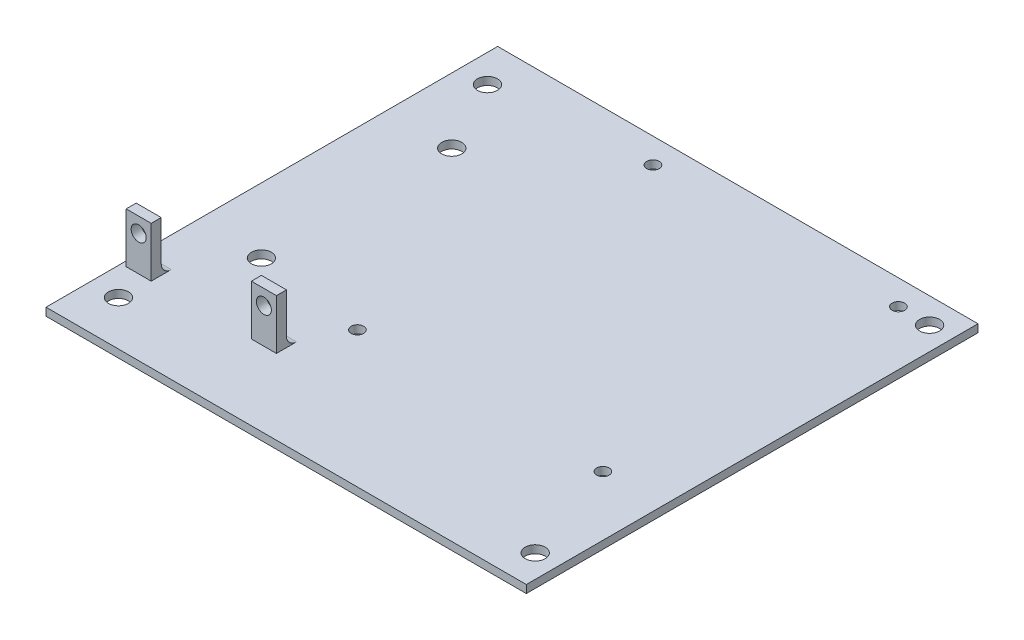
SolidWorks part; units mm, degrees
other "DetailItem3"
material "ABS"
ref_plane "Front Plane" through (0, 0, 0) normal (0, 0, 1) x (1, 0, 0)
ref_plane "Top Plane" through (0, 0, 0) normal (0, 1, 0) x (1, 0, 0)
ref_plane "Right Plane" through (0, 0, 0) normal (1, 0, 0) x (0, 0, -1)
sketch "Sketch1" plane through (0, 0, 0) normal (0, 1, 0) x (1, 0, 0)
  line L1 (-32.2441, 108.719) -> (64.6459, 108.719)
  line L2 (-32.2441, 108.719) -> (-32.2441, 18.549)
  line L3 (-32.2441, 18.549) -> (64.6459, 18.549)
  line L4 (64.6459, 108.719) -> (64.6459, 18.549)
  dimension "D1" = 96.89
  dimension "D2" = 90.17
extrude "PCB" add sketch "Sketch1" along normal blind 1.57
sketch "Sketch2" plane through (0, 1.57, 0) normal (0, 1, 0) x (1, 0, 0)
  line L0 (64.6459, 18.549) -> (64.6459, 108.719) construction
  line L1 (-32.2441, 18.549) -> (64.6459, 18.549) construction
  circle A0 centre (59.5659, 24.899) radius 2
  circle A1 centre (-26.1641, 27.439) radius 2
  circle A2 centre (-26.1641, 101.099) radius 2
  circle A3 centre (59.5659, 103.639) radius 2
  dimension "D3" = 4
  dimension "D6" = 4
  dimension "D11" = 4
  dimension "D12" = 4
  dimension "D1" = 5.08
  dimension "D2" = 6.35
  dimension "D4" = 90.81
  dimension "D5" = 8.89
  dimension "D7" = 90.81
  dimension "D8" = 5.08
  dimension "D9" = 85.09
  dimension "D10" = 82.55
extrude "M3 Mounting Holes" cut sketch "Sketch2" against normal blind 1.57
sketch "Sketch5" plane through (0, 1.57, 0) normal (0, 1, 0) x (1, 0, 0)
  line L0 (64.6459, 108.719) -> (-32.2441, 108.719) construction
  line L1 (-32.2441, 18.549) -> (-31.7441, 18.549)
  line L2 (-32.2441, 18.549) -> (-32.2441, 108.719)
  line L3 (-32.2441, 108.719) -> (-31.7441, 108.719)
  line L4 (-31.7441, 18.549) -> (-31.7441, 108.719)
  line L5 (-32.2441, 18.549) -> (64.6459, 18.549) construction
  line L6 (64.6459, 108.719) -> (64.1459, 108.719)
  line L7 (64.6459, 108.719) -> (64.6459, 18.549)
  line L8 (64.6459, 18.549) -> (64.1459, 18.549)
  line L9 (64.1459, 108.719) -> (64.1459, 18.549)
  dimension "D1" = 0.5
  dimension "D2" = 0.5
extrude "Cut-Extrude1" cut sketch "Sketch5" against normal through all
sketch "Sketch8" plane through (0, 1.57, 0) normal (0, 1, 0) x (1, 0, 0)
  line L1 (-31.7441, 18.549) -> (-31.7441, 108.719) construction
  line L3 (64.1459, 108.719) -> (-31.7441, 108.719) construction
  circle A0 centre (3.2559, 45.719) radius 1.25
  circle A1 centre (52.2559, 45.719) radius 1.25
  circle A2 centre (4.2559, 103.719) radius 1.25
  circle A3 centre (53.2559, 103.719) radius 1.25
  dimension "D1" = 2.5
  dimension "D3" = 2.5
  dimension "D5" = 2.5
  dimension "D6" = 2.5
  dimension "D2" = 5
  dimension "D4" = 63
  dimension "D7" = 58
  dimension "D8" = 58
  dimension "D9" = 49
  dimension "D10" = 35
  dimension "D11" = 36
  dimension "D12" = 49
extrude "RPi mounting hole" cut sketch "Sketch8" against normal blind 10
sketch "Sketch9" plane through (0, 1.57, 0) normal (0, 1, 0) x (1, 0, 0)
  line L0 (-31.7441, 18.549) -> (64.1459, 18.549) construction
  line L1 (-31.7441, 18.549) -> (-31.7441, 108.719) construction
  circle A0 centre (-18.7441, 86.549) radius 2
  circle A1 centre (-18.7441, 48.549) radius 2
  dimension "D1" = 4
  dimension "D2" = 4
  dimension "D3" = 38
  dimension "D4" = 30
  dimension "D5" = 13
  dimension "D6" = 13
extrude "PowerAdapterHoles" cut sketch "Sketch9" against normal blind 10
sketch "Sketch10" plane through (0, 1.57, 0) normal (0, 1, 0) x (1, 0, 0)
  line L0 (-31.7441, 18.549) -> (64.1459, 18.549) construction
  line L1 (-30.7441, 33.549) -> (-25.7441, 33.549)
  line L2 (-30.7441, 33.549) -> (-30.7441, 35.549)
  line L3 (-30.7441, 35.549) -> (-25.7441, 35.549)
  line L4 (-25.7441, 33.549) -> (-25.7441, 35.549)
  line L5 (-0.7441, 33.549) -> (-5.7441, 33.549)
  line L6 (-0.7441, 33.549) -> (-0.7441, 35.549)
  line L7 (-0.7441, 35.549) -> (-5.7441, 35.549)
  line L8 (-5.7441, 33.549) -> (-5.7441, 35.549)
  line L9 (-31.7441, 18.549) -> (-31.7441, 108.719) construction
  dimension "D1" = 2
  dimension "D2" = 2
  dimension "D3" = 5
  dimension "D4" = 5
  dimension "D5" = 20
  dimension "D6" = 15
  dimension "D7" = 15
  dimension "D8" = 1
extrude "DSub Holder" add sketch "Sketch10" along normal blind 10
fillet "Fillet2" radius 2 2 edges at (-28.2441, 1.57, -35.549) (-3.2441, 1.57, -35.549)
sketch "Sketch11" plane through (0, 0, -33.549) normal (0, 0, 1) x (1, 0, 0)
  line L2 (-30.7441, 1.57) -> (-25.7441, 1.57) construction
  line L3 (-5.7441, 1.57) -> (-0.7441, 1.57) construction
  line L4 (-30.7441, 11.57) -> (-30.7441, 1.57) construction
  circle A0 centre (-28.2441, 8.57) radius 1.5
  circle A1 centre (-3.2541, 8.57) radius 1.5
  dimension "D1" = 3
  dimension "D2" = 3
  dimension "D3" = 24.99
  dimension "D4" = 7
  dimension "D5" = 7
  dimension "D6" = 2.5
extrude "DSub Fields" cut sketch "Sketch11" against normal up to next
